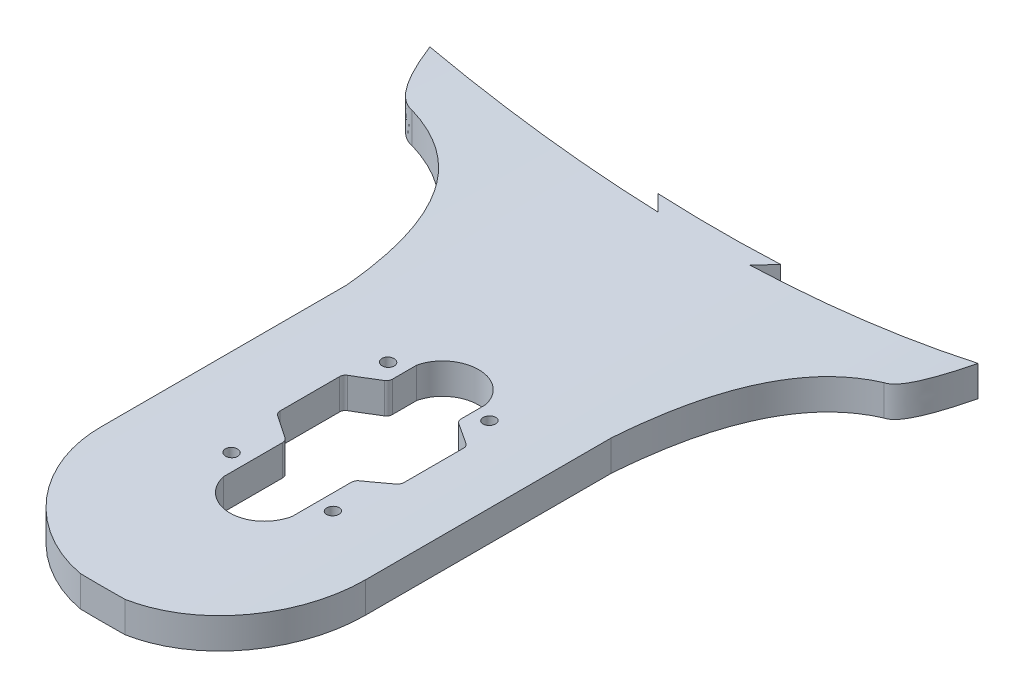
SolidWorks part; units mm, degrees
material "Maple"
ref_plane "Front Plane" through (0, 0, 0) normal (0, 0, 1) x (1, 0, 0)
ref_plane "Top Plane" through (0, 0, 0) normal (0, 1, 0) x (1, 0, 0)
ref_plane "Right Plane" through (0, 0, 0) normal (1, 0, 0) x (0, 0, -1)
sketch "Sketch1" plane through (0, 0, 0) normal (0, 0, 1) x (1, 0, 0)
  line L0 (0, 0) -> (230.1875, 0)
  line L1 (115.0937, 0) -> (115.0937, -12.7)
  line L2 (230.1875, 0) -> (230.1875, -12.7)
  line L3 (0, 0) -> (0, -12.7)
  arc A0 (230.1875, 0) -> (0, 0) centre (115.0938, 515.1686) cw
  arc A1 (230.1875, -12.7) -> (0, -12.7) centre (115.0938, 502.4686) cw
  point P6 (115.0937, -12.7)
  dimension "D1" = 2
extrude "Boss-Extrude1" add sketch "Sketch1" along normal blind 482.6 contours A1 L2 A0 L3 region at (115.0938, -14.8372, 0)
sketch "Sketch2" plane through (0, 0, 0) normal (0, 0, -1) x (-1, 0, 0)
  line L0 (-230.1875, 0) -> (-230.1875, -12.7)
  line L1 (0, 0) -> (0, -12.7)
  line L4 (-60.325, -19.05) -> (-60.325, -9.8511)
  line L5 (-169.8625, -19.05) -> (-169.8625, -9.8511)
  line L6 (-169.8625, -19.05) -> (-169.8625, -22.5511)
  line L7 (-60.325, -22.5511) -> (-60.325, -19.05)
  arc A0 (-230.1875, 0) -> (0, 0) centre (-115.0938, 515.1686) ccw
  arc A1 (-230.1875, -12.7) -> (0, -12.7) centre (-115.0938, 502.4686) ccw
  point P15 (-115.0938, -19.05)
  arc M1 (-230.1875, -12.7) -> (0, -12.7) centre (-115.0938, 502.4686) ccw
  line M2 (0, -12.7) -> (0, 0)
  arc M3 (0, 0) -> (-230.1875, 0) centre (-115.0938, 515.1686) cw
  line M4 (-230.1875, 0) -> (-230.1875, -12.7)
extrude "Boss-Extrude2" add sketch "Sketch2" along normal blind 98.425 contours L6 L5 M3 M4 M1 | L7 L4 M1 M2 M3 region at (200.025, -11.8738, 0) region at (30.1625, -11.8738, 0)
sketch "Sketch3" plane through (0, 0, 0) normal (0, 0, -1) x (-1, 0, 0)
  line L0 (-230.1875, -12.7) -> (-230.1875, 0)
  line L1 (0, 0) -> (0, -12.7)
  line L2 (-169.8625, -9.8511) -> (-169.8625, -22.5511)
  line L3 (-60.325, -9.8511) -> (-60.325, -22.5511)
  arc A0 (-230.1875, 0) -> (0, 0) centre (-115.0937, 515.1686) ccw
  arc A1 (-230.1875, -12.7) -> (0, -12.7) centre (-115.0938, 502.4686) ccw
  arc M1 (-169.8625, -22.5511) -> (-60.325, -22.5511) centre (-115.0938, 502.4686) ccw
  line M2 (-60.325, -22.5511) -> (-60.325, -9.8511)
  arc M3 (-60.325, -9.8511) -> (-169.8625, -9.8511) centre (-115.0938, 515.1686) cw
  line M4 (-169.8625, -9.8511) -> (-169.8625, -22.5511)
extrude "Boss-Extrude3" add sketch "Sketch3" along normal blind 254 contours M4 M1 M2 M3 region at (115.0938, -18.1014, 0)
sketch "Sketch4" plane through (0, 0, 482.6) normal (0, 0, 1) x (1, 0, 0)
  line L0 (0, 0) -> (0, -12.7)
  line L1 (230.1875, -12.7) -> (230.1875, 0)
  line L2 (60.325, -22.5511) -> (60.325, -9.8511)
  line L3 (169.8625, -22.5511) -> (169.8625, -9.8511)
  arc A0 (0, 0) -> (230.1875, 0) centre (115.0938, 515.1686) ccw
  arc A1 (0, -12.7) -> (230.1875, -12.7) centre (115.0938, 502.4686) ccw
  point P15 (115.0937, -19.05)
  arc M1 (0, -12.7) -> (230.1875, -12.7) centre (115.0938, 502.4686) ccw
  arc M3 (230.1875, 0) -> (0, 0) centre (115.0938, 515.1686) cw
extrude "Boss-Extrude4" add sketch "Sketch4" along normal blind 254 contours L3 L2 M1 M3 region at (115.0937, -18.1014, 482.6)
sketch "Sketch5" plane through (0, 0, 482.6) normal (0, 0, 1) x (1, 0, 0)
  line L0 (0, 0) -> (0, -12.7)
  line L1 (60.325, -9.8511) -> (60.325, -22.5511)
  line L2 (230.1875, 0) -> (230.1875, -12.7)
  line L3 (169.8625, -9.8511) -> (169.8625, -22.5511)
  arc A0 (0, 0) -> (230.1875, 0) centre (115.0938, 515.1686) ccw
  arc A1 (0, -12.7) -> (230.1875, -12.7) centre (115.0938, 502.4686) ccw
  arc M1 (0, -12.7) -> (60.325, -22.5511) centre (115.0938, 502.4686) ccw
  line M2 (60.325, -22.5511) -> (60.325, -9.8511)
  arc M3 (60.325, -9.8511) -> (0, 0) centre (115.0938, 515.1686) cw
  line M4 (0, 0) -> (0, -12.7)
extrude "Boss-Extrude5" add sketch "Sketch5" along normal blind 98.425 contours M4 M1 M2 M3 | L3 A1 L2 A0 region at (30.1625, -11.8738, 482.6) region at (200.025, -11.8738, 482.6)
ref_plane "Plane1" through (0, 0, 0) normal (0, -1, 0) x (-1, 0, 0)
sketch "Sketch6" plane through (0, 0, 0) normal (0, -1, 0) x (-1, 0, 0)
  line L0 (-115.0937, -736.6) -> (-115.0937, -482.6) construction
  line L1 (-169.8625, -736.6) -> (-60.325, -736.6) construction
  line L2 (-115.0938, 254) -> (-115.0937, 0) construction
  line L3 (-60.325, 254) -> (-169.8625, 254) construction
  line L4 (-230.1875, -482.6) -> (0, -482.6) construction
  line L5 (0, -581.025) -> (0, 98.425) construction
  line L6 (-230.1875, 0) -> (0, 0) construction
  line L7 (-60.325, -581.025) -> (0, -482.6) construction
  line L8 (-60.325, -736.6) -> (-60.325, -581.025) construction
  line L9 (-60.325, -682.625) -> (-169.8625, -682.625) construction
  line L10 (-169.8625, -736.6) -> (-169.8625, -581.025) construction
  line L11 (-169.8625, -581.025) -> (-230.1875, -482.6) construction
  line L12 (-60.325, 254) -> (-60.325, 98.425) construction
  line L13 (-60.325, 200.025) -> (-169.8625, 200.025) construction
  line L14 (-169.8625, 254) -> (-169.8625, 98.425) construction
  line L15 (-30.1625, -531.8125) -> (-200.025, -531.8125) construction
  line L16 (-230.1875, 0) -> (-169.8625, 98.425) construction
  line L17 (-60.325, 98.425) -> (0, 0) construction
  line L18 (-200.025, 49.2125) -> (-30.1625, 49.2125) construction
  line L19 (-30.1625, -531.8125) -> (-230.1875, -482.6) construction
  line L20 (-200.025, -531.8125) -> (0, -482.6) construction
  line L21 (0, 0) -> (-200.025, 49.2125) construction
  line L22 (-30.1625, 49.2125) -> (-230.1875, 0) construction
  line L23 (-230.1875, -510.9167) -> (0, -510.9167) construction
  line L24 (-230.1875, 28.3167) -> (0, 28.3167) construction
  line L25 (0, 0) -> (-8.6777, 28.3167) construction
  line L26 (-17.3554, -510.9167) -> (-8.6777, -510.9167) construction
  line L27 (-221.5098, 28.3167) -> (-230.1875, 0) construction
  line L28 (-8.6777, -510.9167) -> (0, -482.6) construction
  line L29 (-230.1875, -482.6) -> (-221.5098, -510.9167) construction
  line L30 (-212.8321, -510.9167) -> (-221.5098, -510.9167) construction
  line L31 (-8.6777, -510.9167) -> (0, -482.6) construction
  line L32 (-221.5098, -510.9167) -> (-230.1875, -482.6) construction
  line L33 (-17.3554, 28.3167) -> (-8.6777, 28.3167) construction
  line L34 (-8.6777, 28.3167) -> (0, 0) construction
  line L35 (-212.8321, 28.3167) -> (-221.5098, 28.3167) construction
  line L36 (-221.5098, 28.3167) -> (-230.1875, 0) construction
  line L38 (-60.325, -581.025) -> (0, -581.025)
  line L39 (0, -581.025) -> (0, -510.9167)
  line L40 (-60.325, -682.625) -> (-60.325, -736.6)
  line L41 (-60.325, -736.6) -> (-169.8625, -736.6)
  line L42 (-169.8625, -736.6) -> (-169.8625, -682.625)
  line L43 (-169.8625, -581.025) -> (-230.1875, -581.025)
  line L44 (-230.1875, -581.025) -> (-230.1875, -510.9167)
  line L45 (-230.1875, 0) -> (-230.1875, 98.425)
  line L46 (-230.1875, 98.425) -> (-169.8625, 98.425)
  line L47 (-169.8625, 200.025) -> (-169.8625, 254)
  line L48 (-169.8625, 254) -> (-60.325, 254)
  line L49 (-60.325, 254) -> (-60.325, 200.025)
  line L50 (-60.325, 98.425) -> (0, 98.425)
  line L51 (0, 98.425) -> (0, 0)
  line L52 (-230.1875, -482.6) -> (-230.1875, -510.9167)
  line L53 (0, -482.6) -> (0, -510.9167)
  arc A0 (-60.325, -682.625) -> (-169.8625, -682.625) centre (-115.0937, -682.625) cw
  arc A1 (-60.325, 200.025) -> (-169.8625, 200.025) centre (-115.0938, 200.025) ccw
  spline S0 degree 2 poles (-60.325, -581.025) (-55.0487, -517.0259) (-17.3554, -510.9167) knots 0 0 0 0.825721 0.825721 0.825721
  spline S1 degree 2 poles (-169.8625, -581.025) (-175.1388, -517.0259) (-212.8321, -510.9167) knots 0 0 0 0.825721 0.825721 0.825721
  spline S2 degree 2 poles (-169.8625, 98.425) (-175.1388, 34.4259) (-212.8321, 28.3167) knots 0 0 0 0.825721 0.825721 0.825721
  spline S3 degree 2 poles (-60.325, 98.425) (-55.0487, 34.4259) (-17.3554, 28.3167) knots 0 0 0 0.825721 0.825721 0.825721
  spline S4 degree 2 poles (-17.3554, -510.9167) (-8.6777, -510.9167) (0, -482.6) knots 0 0 0 1 1 1
  spline S5 degree 2 poles (-212.8321, -510.9167) (-221.5098, -510.9167) (-230.1875, -482.6) knots 0 0 0 1 1 1
  spline S6 degree 2 poles (-17.3554, 28.3167) (-8.6777, 28.3167) (0, 0) knots 0 0 0 1 1 1
  spline S7 degree 2 poles (-212.8321, 28.3167) (-221.5098, 28.3167) (-230.1875, 0) knots 0 0 0 1 1 1
  point P13 (-115.0937, -482.6)
  point P17 (-115.0937, 0)
  point P43 (-115.0938, -510.9167)
  point P44 (-17.3554, -510.9167)
  point P45 (-115.0938, 28.3167)
  point P49 (-115.0938, -510.9167)
  point P51 (-115.0938, 28.3167)
  point P53 (-212.8321, -510.9167)
  point P54 (-212.8321, 28.3167)
  point P55 (-17.3554, 28.3167)
extrude "Cut-Extrude1" cut sketch "Sketch6" along normal blind 98.425 contours L40 A0 L41 | L41 A0 L42 | S1 S5 L52 L44 L43 | S4 S0 L38 L39 L53 | S3 S6 L51 L50 | S7 S2 L46 L45 | A1 L48 L47 | A1 L49 L48 region at (25.0997, 0, 547.5668) region at (158.3996, 0, 724.4055) region at (71.7879, 0, 724.4055) region at (205.0878, 0, 547.5668) region at (205.0878, 0, -64.9668) region at (71.7879, 0, -241.8055) region at (158.3996, 0, -241.8055) region at (25.0997, 0, -64.9668)
sketch "Sketch8" plane through (0, 0, 0) normal (0, -1, 0) x (-1, 0, 0)
  line L0 (-60.325, 98.425) -> (-169.8625, 98.425) construction
  line L1 (0, 0) -> (-230.1875, 0) construction
  line L2 (-100.8698, 189.865) -> (-100.8698, 163.957)
  line L3 (-115.0938, 98.425) -> (-115.0937, 0)
  line L4 (0, -482.6) -> (-230.1875, -482.6)
  line L5 (0, -241.3) -> (-230.1875, -241.3)
  line L6 (0, -482.6) -> (0, 0) construction
  line L7 (-230.1875, -482.6) -> (-230.1875, 0) construction
  line L8 (-100.8698, 163.957) -> (-89.4398, 156.337)
  line L9 (-89.4398, 156.337) -> (-89.4398, 128.905)
  line L10 (-89.4398, 128.905) -> (-100.8698, 121.285)
  line L11 (-100.8698, 121.285) -> (-100.8698, 109.855)
  line L12 (-129.3177, 109.855) -> (-129.3177, 121.285)
  line L13 (-129.3177, 121.285) -> (-140.7477, 128.905)
  line L14 (-140.7477, 128.905) -> (-140.7477, 156.337)
  line L15 (-140.7477, 156.337) -> (-129.3177, 163.957)
  line L16 (-129.3177, 163.957) -> (-129.3177, 189.865)
  line L17 (-115.0938, 98.425) -> (-115.0938, 114.935) construction
  line L18 (-115.0938, 201.295) -> (-115.0938, 179.705) construction
  line L19 (-94.1388, 179.705) -> (-136.0488, 179.705) construction
  line L20 (-94.1388, 114.935) -> (-136.0488, 114.935) construction
  line L21 (-94.1387, -597.535) -> (-136.0487, -597.535) construction
  line L22 (-94.1387, -662.305) -> (-136.0487, -662.305) construction
  line L23 (-115.0937, -683.895) -> (-115.0937, -662.305) construction
  line L24 (-115.0937, -581.025) -> (-115.0937, -597.535) construction
  line L25 (-129.3177, -646.557) -> (-129.3177, -672.465)
  line L26 (-140.7477, -638.937) -> (-129.3177, -646.557)
  line L27 (-140.7477, -611.505) -> (-140.7477, -638.937)
  line L28 (-129.3177, -603.885) -> (-140.7477, -611.505)
  line L29 (-129.3177, -592.455) -> (-129.3177, -603.885)
  line L30 (-100.8698, -603.885) -> (-100.8698, -592.455)
  line L31 (-89.4398, -611.505) -> (-100.8698, -603.885)
  line L32 (-89.4398, -638.937) -> (-89.4398, -611.505)
  line L33 (-100.8698, -646.557) -> (-89.4398, -638.937)
  line L34 (-100.8698, -672.465) -> (-100.8698, -646.557)
  arc A0 (-100.8698, 189.865) -> (-129.3177, 189.865) centre (-115.0938, 186.7295) ccw
  arc A1 (-100.8698, 109.855) -> (-129.3177, 109.855) centre (-115.0938, 112.9905) cw
  circle A2 centre (-136.0488, 179.705) radius 2.54
  circle A3 centre (-136.0488, 114.935) radius 2.54
  circle A4 centre (-94.1388, 114.935) radius 2.54
  circle A5 centre (-94.1388, 179.705) radius 2.54
  circle A6 centre (-94.1387, -597.535) radius 2.54
  circle A7 centre (-136.0487, -597.535) radius 2.54
  circle A8 centre (-136.0487, -662.305) radius 2.54
  arc A9 (-100.8698, -592.455) -> (-129.3177, -592.455) centre (-115.0937, -595.5905) ccw
  arc A10 (-100.8698, -672.465) -> (-129.3177, -672.465) centre (-115.0937, -669.3295) cw
  circle A11 centre (-94.1387, -662.305) radius 2.54
  point P26 (-115.0937, 189.865)
  point P29 (-115.0938, 201.295)
  point P30 (-115.0938, 98.425)
  point P42 (-115.0938, 179.705)
  point P46 (-115.0938, 114.935)
  point P47 (-100.8698, 163.957)
  point P48 (-89.4398, 156.337)
  point P49 (-89.4398, 128.905)
  point P50 (-100.8698, 121.285)
  point P51 (-100.8698, 109.855)
  point P52 (-129.3177, 109.855)
  point P53 (-129.3177, 121.285)
  point P54 (-140.7477, 128.905)
  point P55 (-140.7477, 156.337)
  point P56 (-129.3177, 163.957)
  point P57 (-129.3177, 189.865)
  point P58 (-100.8698, 189.865)
  point P59 (-100.8698, 163.957)
  point P60 (-89.4398, 156.337)
  point P87 (-115.0937, -672.465)
extrude "Cut-Extrude2" cut sketch "Sketch8" along normal blind 30.48 contours A1 L11 L10 L9 L8 L2 A0 L16 L15 L14 L13 L12 | A4 | A10 L34 L33 L32 L31 L30 A9 L29 L28 L27 L26 L25 | A2 | A5 | A3 | A11 | A8 | A6 | A7 region at (115.0937, 0, -148.2319) region at (115.0937, 0, 630.8319) region at (94.1388, 0, -114.935)
fillet "Fillet2" radius 2.54 16 edges at (100.8698, -18.8583, -121.285) (89.4398, -18.4262, -128.905) (89.4398, -18.4262, -156.337) (100.8698, -18.8583, -163.957) (129.3177, -18.8583, -121.285) (140.7477, -18.4262, -128.905) (140.7477, -18.4262, -156.337) (129.3177, -18.8583, -163.957) (140.7477, -18.4262, 638.937) (140.7477, -18.4262, 611.505) (89.4398, -18.4262, 638.937) (89.4398, -18.4262, 611.505) (129.3177, -18.8583, 646.557) (129.3177, -18.8583, 603.885) (100.8698, -18.8583, 646.557) (100.8698, -18.8583, 603.885)
fillet "Fillet1" radius 7.62 4 edges at (0, -6.35, 0) (0, -6.35, 482.6) (230.1875, -6.35, 0) (230.1875, -6.35, 482.6)
sketch "Sketch9" plane through (0, 0, 0) normal (0, -1, 0) x (-1, 0, 0)
  line L0 (-115.0937, -736.6) -> (-115.0938, -88.7823) construction
  line L1 (-124.3844, -736.6) -> (-105.8031, -736.6) construction
  line L2 (-105.8031, 254) -> (-124.3844, 254) construction
  line L3 (0, -481.4477) -> (-230.1875, -481.4477) construction
  line L4 (-230.1875, -1.1523) -> (0, -1.1523) construction
  line L5 (-115.0937, -481.4477) -> (-115.0938, -470.0177) construction
  line L6 (-115.0938, -470.0177) -> (-115.0938, -400.1677) construction
  line L7 (0, -241.3) -> (-230.1875, -241.3) construction
  line L8 (0, -481.4477) -> (0, -1.1523) construction
  line L9 (-230.1875, -481.4477) -> (-230.1875, -1.1523) construction
  line L10 (-115.0938, -76.0823) -> (-115.0938, 254) construction
  circle A4 centre (-115.0938, -444.6177) radius 6.35
  circle A5 centre (-115.0938, -374.7677) radius 6.35
  circle A6 centre (-115.0938, -107.8323) radius 6.35
  circle A7 centre (-115.0938, -37.9823) radius 6.35
  point P23 (-115.0937, -82.4323)
  point P24 (-115.0937, -12.5823)
extrude "Cut-Extrude3" cut sketch "Sketch9" along normal blind 38.1
sketch "Sketch10" plane through (0, 0, 0) normal (0, -1, 0) x (-1, 0, 0)
  line L0 (0, -481.4477) -> (-230.1875, -481.4477) construction
  line L1 (-230.1875, -1.1523) -> (0, -1.1523) construction
  line L2 (0, -241.3) -> (-230.1875, -241.3) construction
  line L3 (0, -481.4477) -> (0, -1.1523) construction
  line L4 (-230.1875, -481.4477) -> (-230.1875, -1.1523) construction
  line L5 (-140.4937, -481.4477) -> (-89.6937, -481.4477)
  line L6 (-96.0437, -487.7977) -> (-1.6735, -487.7977)
  line L7 (-134.1437, -487.7977) -> (-228.514, -487.7977)
  line L10 (-134.1437, -487.7977) -> (-140.4937, -481.4477)
  line L11 (-96.0437, -487.7977) -> (-89.6937, -481.4477)
  line L12 (-134.1437, 5.1977) -> (-140.4937, -1.1523)
  line L13 (-134.1437, 5.1977) -> (-228.514, 5.1977)
  line L14 (-140.4937, -1.1523) -> (-89.6937, -1.1523)
  line L15 (-96.0438, 5.1977) -> (-89.6937, -1.1523)
  line L16 (-96.0438, 5.1977) -> (-1.6735, 5.1977)
  line L17 (-1.6735, -487.7977) -> (6.5793, -487.7977)
  line L18 (-1.6735, -487.7977) -> (-228.514, -487.7977)
  line L19 (-1.6735, -487.7977) -> (-1.6735, -743.3709)
  line L20 (-1.6735, -743.3709) -> (-228.514, -743.3709)
  line L21 (-228.514, -487.7977) -> (-228.514, -743.3709)
  line L22 (-228.514, 5.1977) -> (-1.6735, 5.1977)
  line L23 (-228.514, 5.1977) -> (-228.514, 264.7545)
  line L24 (-228.514, 264.7545) -> (-1.6735, 264.7545)
  line L25 (-1.6735, 5.1977) -> (-1.6735, 264.7545)
  line L26 (6.5793, -487.7977) -> (6.5793, 5.1977)
  line L27 (6.5793, 5.1977) -> (-1.6735, 5.1977)
  line L28 (-228.514, 5.1977) -> (-237.2959, 5.1977)
  line L29 (-237.2959, 5.1977) -> (-237.2959, -487.7977)
  line L30 (-237.2959, -487.7977) -> (-228.514, -487.7977)
  parabola Q0 (-0.3473, -483.7219) -> (-17.3554, -510.9167) focus (-17.3554, -508.2574) apex (-17.3554, -510.9167) construction
  parabola Q1 (-229.8402, -483.7219) -> (-212.8321, -510.9167) focus (-212.8321, -508.2574) apex (-212.8321, -510.9167) construction
  point P17 (-115.0937, -481.4477)
  point P20 (-89.6937, -481.4477)
  point P24 (-140.4937, -481.4477)
extrude "Cut-Extrude5" cut sketch "Sketch10" along normal blind 38.1 contours L29 L30 L7 L10 L5 L11 L6 L17 L26 L27 L16 L15 L14 L12 L13 L28 | L16 L25 L24 L23 L13 L22 | L22 L12 L14 L15 region at (115.3595, 0, 241.3) region at (115.0938, 0, -134.9761) region at (115.0938, 0, -1.8715)
